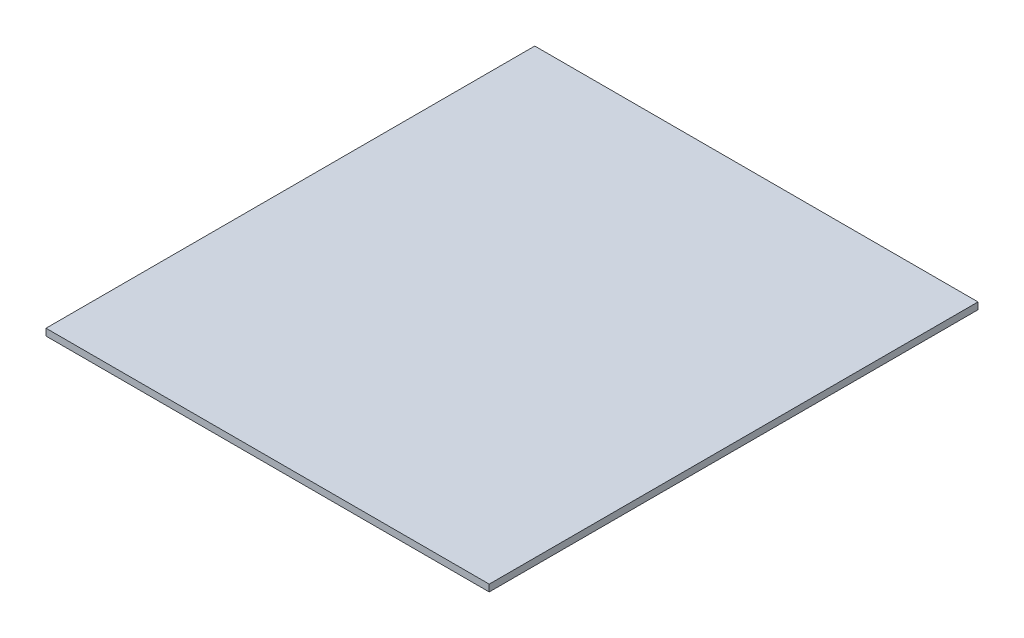
SolidWorks part; units mm, degrees
material "Acrylic (Medium-high impact)"
ref_plane "Front" through (0, 0, 0) normal (0, 0, 1) x (1, 0, 0)
ref_plane "Top" through (0, 0, 0) normal (0, 1, 0) x (1, 0, 0)
ref_plane "Right" through (0, 0, 0) normal (1, 0, 0) x (0, 0, -1)
sketch "Sketch1" plane through (0, 0, 0) normal (0, 1, 0) x (1, 0, 0)
  line L1 (-103.1875, -113.792) -> (103.1875, -113.792)
  line L2 (-103.1875, -113.792) -> (-103.1875, 113.792)
  line L3 (-103.1875, 113.792) -> (103.1875, 113.792)
  line L4 (103.1875, -113.792) -> (103.1875, 113.792)
  line L5 (-103.1875, -113.792) -> (103.1875, 113.792) construction
  line L6 (-103.1875, 113.792) -> (103.1875, -113.792) construction
  point P0 (0, 0)
  dimension "D1" = 206.375
  dimension "D2" = 227.584
extrude "Boss-Extrude1" add sketch "Sketch1" along normal blind 3.175
